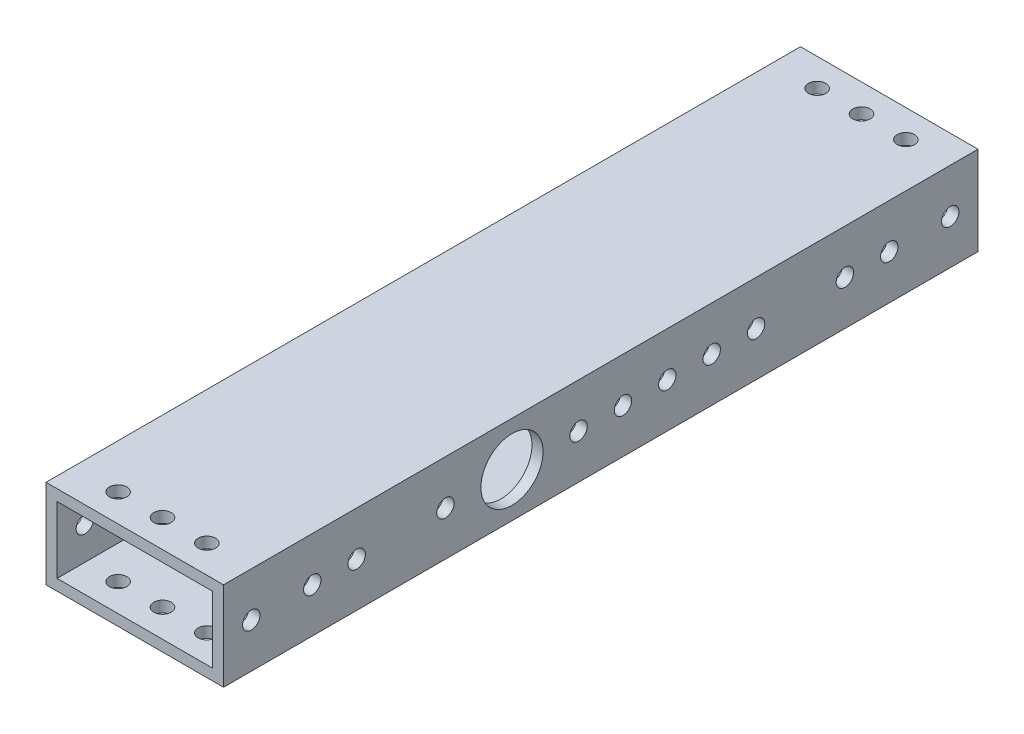
SolidWorks part; units mm, degrees
material "6061-T6 (SS)"
ref_plane "Front Plane" through (0, 0, 0) normal (0, 0, 1) x (1, 0, 0)
ref_plane "Top Plane" through (0, 0, 0) normal (0, 1, 0) x (1, 0, 0)
ref_plane "Right Plane" through (0, 0, 0) normal (1, 0, 0) x (0, 0, -1)
sketch "Sketch1" plane through (0, 0, 0) normal (0, 0, 1) x (1, 0, 0)
  line L0 (-22.225, 9.525) -> (22.225, 9.525)
  line L1 (-25.4, -12.7) -> (25.4, -12.7)
  line L2 (-25.4, -12.7) -> (-25.4, 12.7)
  line L3 (-25.4, 12.7) -> (25.4, 12.7)
  line L4 (25.4, -12.7) -> (25.4, 12.7)
  line L5 (-25.4, -12.7) -> (25.4, 12.7) construction
  line L6 (-25.4, 12.7) -> (25.4, -12.7) construction
  line L7 (22.225, -9.525) -> (22.225, 9.525)
  line L8 (-22.225, -9.525) -> (22.225, -9.525)
  line L9 (-22.225, -9.525) -> (-22.225, 9.525)
  point P0 (0, 0)
  dimension "D1" = 50.8
  dimension "D2" = 25.4
  dimension "D3" = 3.175
extrude "Boss-Extrude1" add sketch "Sketch1" along normal mid plane 215.9
sketch "Sketch3" plane through (0, 12.7, 0) normal (0, 1, 0) x (1, 0, 0)
  line L0 (-25.4, 0) -> (25.4, 0) construction
  line L1 (-25.4, -107.95) -> (-25.4, 107.95) construction
  line L2 (25.4, -107.95) -> (25.4, 107.95) construction
  line L3 (25.4, -107.95) -> (-25.4, -107.95) construction
  circle A0 centre (-12.7, -100.0125) radius 2.4892
  circle A1 centre (0, -100.0125) radius 2.4892
  circle A2 centre (12.7, -100.0125) radius 2.4892
  circle A3 centre (12.7, 100.0125) radius 2.4892
  circle A4 centre (0, 100.0125) radius 2.4892
  circle A5 centre (-12.7, 100.0125) radius 2.4892
  dimension "D1" = 4.9784
  dimension "D2" = 12.7
  dimension "D3" = 12.7
  dimension "D4" = 7.9375
extrude "Cut-Extrude2" cut sketch "Sketch3" against normal through all
sketch "Sketch4" plane through (25.4, 0, 0) normal (1, 0, 0) x (0, 0, -1)
  line L0 (-25.4, 0) -> (-45.1908, 0) construction
  line L1 (-16.51, 0) -> (-34.29, 0) construction
  line L8 (-25.4, 0) -> (31.75, 0) construction
  line L9 (0, 12.7) -> (0, -12.7) construction
  line L10 (-107.95, 12.7) -> (107.95, 12.7) construction
  line L11 (-107.95, -12.7) -> (107.95, -12.7) construction
  circle A0 centre (-25.4, 0) radius 8.89
  circle A9 centre (31.75, 0) radius 2.4892
  circle A10 centre (19.05, 0) radius 2.4892
  dimension "D2" = 17.78
  dimension "D3" = 25.4
  dimension "D1" = 57.15
  dimension "D4" = 4.9784
  dimension "D6" = 44.45
extrude "Cut-Extrude3" cut sketch "Sketch4" against normal through all contours A0 | A9 | A10
sketch "Sketch2" plane through (25.4, 0, 0) normal (1, 0, 0) x (0, 0, -1)
  line L0 (-107.95, -12.7) -> (-107.95, 12.7) construction
  line L1 (0, 12.7) -> (0, -12.7) construction
  line L2 (-107.95, 12.7) -> (107.95, 12.7) construction
  line L3 (-107.95, -12.7) -> (107.95, -12.7) construction
  circle A0 centre (-100.0125, 0) radius 2.4892
  circle A1 centre (100.0125, 0) radius 2.4892
  circle A2 centre (-82.55, 0) radius 2.4892
  circle A3 centre (-69.85, 0) radius 2.4892
  circle A4 centre (69.85, 0) radius 2.4892
  circle A5 centre (82.55, 0) radius 2.4892
  dimension "D2" = 4.9784
  dimension "D5" = 4.9784
  dimension "D4" = 25.4
  dimension "D1" = 7.9375
  dimension "D3" = 12.7
extrude "Cut-Extrude1" cut sketch "Sketch2" against normal through all
sketch "Sketch5" plane through (0, -12.7, 0) normal (0, -1, 0) x (1, 0, 0)
  line L0 (-25.4, 107.95) -> (-25.4, -107.95) construction
  line L1 (-25.4, 107.95) -> (25.4, 107.95) construction
  line L4 (25.4, 25.4) -> (-25.4, 25.4) construction
  line L5 (25.4, 107.95) -> (25.4, -107.95) construction
  circle A0 centre (-3.81, 69.85) radius 2.4892
  circle A1 centre (-16.51, 69.85) radius 2.4892
  circle A2 centre (-16.51, 57.15) radius 2.4892
  circle A3 centre (-3.81, 57.15) radius 2.4892
  circle A8 centre (-3.81, -6.35) radius 2.4892
  circle A9 centre (-16.51, -6.35) radius 2.4892
  circle A10 centre (-16.51, -19.05) radius 2.4892
  circle A11 centre (-3.81, -19.05) radius 2.4892
  dimension "D3" = 4.9784
  dimension "D4" = 8.89
  dimension "D7" = 12.7
  dimension "D12" = 82.55
  dimension "D5" = 31.75
  dimension "D6" = 12.7
  dimension "D1" = 2
  dimension "D2" = 2
extrude "Cut-Extrude4" cut sketch "Sketch5" against normal up to next
sketch "Sketch7" plane through (25.4, 0, 0) normal (1, 0, 0) x (0, 0, -1)
  circle A0 centre (44.45, 0) radius 2.4892
  circle A1 centre (31.75, 0) radius 2.4892 construction
  circle A5 centre (6.35, 0) radius 2.4892
  circle A6 centre (-6.35, 0) radius 2.4892
  circle A7 centre (-44.45, 0) radius 2.4892
  circle A8 centre (-25.4, 0) radius 8.89 construction
  dimension "D1" = 12.7
  dimension "D2" = 19.05
  dimension "D3" = 19.05
  dimension "D4" = 12.7
extrude "Cut-Extrude5" cut sketch "Sketch7" against normal up to next contours A0 | A7 | A6 | A5
